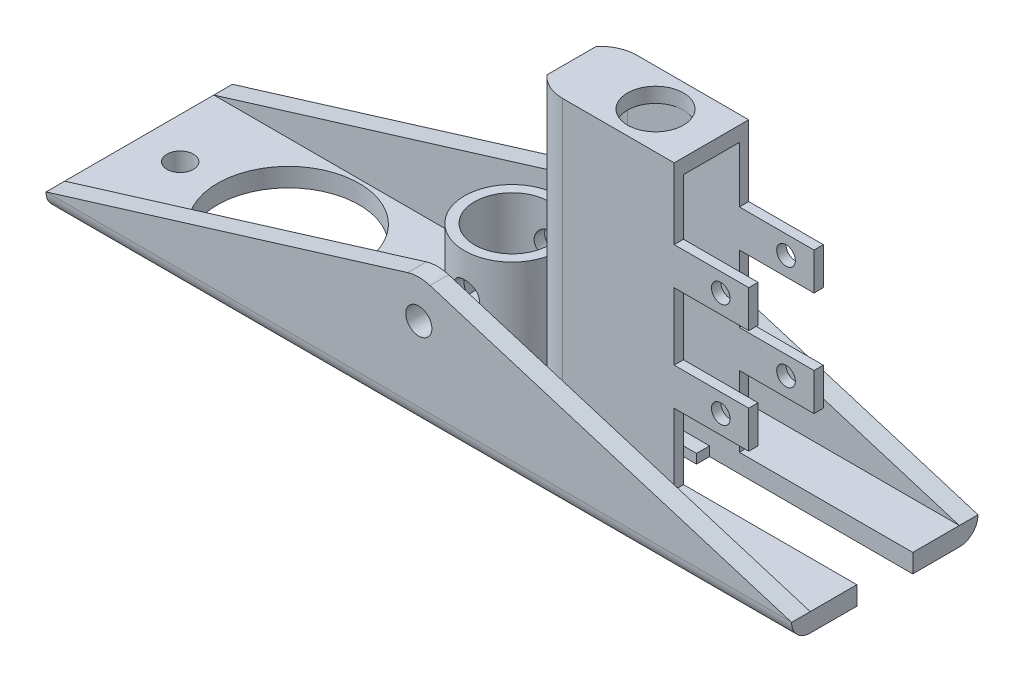
SolidWorks part; units mm, degrees
material "AISI 1035 Steel (SS)"
ref_plane "Front Plane" through (0, 0, 0) normal (0, 0, 1) x (1, 0, 0)
ref_plane "Top Plane" through (0, 0, 0) normal (0, 1, 0) x (1, 0, 0)
ref_plane "Right Plane" through (0, 0, 0) normal (1, 0, 0) x (0, 0, -1)
sketch "Sketch2" plane through (0, 0, 0) normal (0, 1, 0) x (1, 0, 0)
  line L0 (-100, -25) -> (100, -25)
  line L1 (100, -25) -> (100, 25)
  line L2 (100, 25) -> (-100, 25)
  line L3 (-100, 25) -> (-100, -25)
  line L4 (-60, 25) -> (-60, -25) construction
  line L6 (0, -55) -> (0, 55) construction
  circle A1 centre (-60, 0) radius 19
  circle A2 centre (-31, 0) radius 3.55
  circle A3 centre (-89, 0) radius 3.55
  point P6 (-100, 0)
  point P12 (0, 25)
  dimension "D4" = 38
  dimension "D5" = 7.1
  dimension "D1" = 200
  dimension "D2" = 50
  dimension "D6" = 29
  dimension "D3" = 60
extrude "Boss-Extrude1" add sketch "Sketch2" along normal blind 5
sketch "Sketch6" plane through (0, 0, 0) normal (0, 0, 1) x (1, 0, 0)
  line L0 (-100, 5) -> (-2.9907, 34.7517)
  line L1 (2.9907, 34.7517) -> (100, 5)
  line L2 (100, 5) -> (100, 0) construction
  line L3 (-100, 5) -> (100, 5)
  line L4 (-100, 5) -> (-100, 0) construction
  line L5 (55, 0) -> (-55, 0) construction
  arc A0 (2.9907, 34.7517) -> (-2.9907, 34.7517) centre (0, 25) ccw
  point P11 (0, 5)
  dimension "D1" = 20.4
  dimension "D2" = 20
  dimension "D4" = 5
extrude "Boss-Extrude3" add sketch "Sketch6" against normal up to surface and the other way up to surface up to face at (0, 2.5, -25) other way up to face at (0, 2.5, 25)
sketch "Sketch7" plane through (0, 0, 0) normal (0, 0, 1) x (1, 0, 0)
  line L0 (2.9907, 34.7517) -> (100, 5) construction
  line L1 (-100, 5) -> (-2.9907, 34.7517) construction
  line L2 (2.9907, 34.7517) -> (100, 5)
  line L3 (-100, 5) -> (-2.9907, 34.7517)
  line L4 (-100, 5) -> (100, 5)
  arc A0 (2.9907, 34.7517) -> (-2.9907, 34.7517) centre (0, 25) ccw construction
  arc A1 (2.9907, 34.7517) -> (-2.9907, 34.7517) centre (0, 25) ccw
extrude "Cut-Extrude2" cut sketch "Sketch7" against normal offset from surface 5 and the other way offset from surface 5 contours L2 A1 L3 L4 region at (0, 15.2168, 0) up to face at (0, 13.3253, -25) other way up to face at (0, 13.3253, 25)
sketch "Sketch22" [suppressed] plane through (0, 0, 0) normal (0, 0, 1) x (1, 0, 0)
  line L10 (-25.5, 27.8483) -> (-25.5, 5)
  line L11 (0, -19.36) -> (0, 19.36) construction
  line L13 (-100, 5) -> (-25.5, 5)
  line L14 (-100, 5) -> (-2.9907, 34.7517) construction
  line L15 (-25.5, 27.8483) -> (-100, 5)
  dimension "D1" = 25.5
extrude "Cut-Extrude9" [suppressed] cut sketch "Sketch22" against normal offset from surface 5 and the other way offset from surface 5
sketch "Sketch8" plane through (0, 5, 0) normal (0, 1, 0) x (1, 0, 0)
  circle A0 centre (0, 0) radius 10.05
  circle A1 centre (0, 0) radius 12.75
  dimension "D1" = 20.1
  dimension "D2" = 25.5
extrude "Boss-Extrude4" add sketch "Sketch8" along normal blind 30.2
fillet "Fillet1" radius 5 2 edges at (0, 0, -25) (0, 0, 25)
sketch "Sketch9" plane through (0, 0, 25) normal (0, 0, 1) x (1, 0, 0)
  line L0 (0, -55) -> (0, 55) construction
  line L1 (-100, 5) -> (100, 5) construction
  circle A0 centre (0, 25) radius 3.5
  dimension "D2" = 20
  dimension "D1" = 7
extrude "Cut-Extrude3" cut sketch "Sketch9" against normal through all
sketch "Sketch13" plane through (0, 5, 0) normal (0, 1, 0) x (1, 0, 0)
  line L0 (23.5, 0) -> (53.5, 0) construction
  line L1 (23.5, 7.5) -> (53.5, 7.5)
  line L2 (23.5, -7.5) -> (53.5, -7.5)
  arc A0 (23.5, 7.5) -> (23.5, -7.5) centre (23.5, 0) ccw
  arc A1 (53.5, -7.5) -> (53.5, 7.5) centre (53.5, 0) ccw
  circle A2 centre (31.5, 0) radius 2
  circle A4 centre (24.5, 0) radius 2
  circle A5 centre (38.5, 0) radius 2
  circle A6 centre (45.5, 0) radius 2
  circle A7 centre (52.5, 0) radius 2
  point P3 (38.5, 0)
  point P8 (16, 0)
  point P24 (38.5, 7.5)
  dimension "D3" = 16
  dimension "D4" = 4
  dimension "D1" = 30
  dimension "D2" = 7.5
  dimension "D6" = 7
  dimension "D5" = 5
extrude "Cut-Extrude5" cut sketch "Sketch13" against normal blind 2.5
sketch "Sketch15" plane through (0, 5, 0) normal (0, 1, 0) x (1, 0, 0)
  line L0 (23.5, 0) -> (53.5, 0) construction
  line L1 (23.5, 4) -> (53.5, 4)
  line L2 (23.5, -4) -> (53.5, -4)
  line L3 (53.5, 7.5) -> (23.5, 7.5) construction
  line L4 (53.5, 4) -> (100, 4)
  line L5 (100, 20) -> (100, -20) construction
  line L6 (100, 4) -> (100, -4)
  line L7 (100, -4) -> (53.5, -4)
  arc A5 (23.5, 4) -> (23.5, -4) centre (23.5, 0) ccw
  point P3 (38.5, 0)
  point P6 (100, 0)
  point P14 (38.5, 4)
  point P23 (38.5, 7.5)
  dimension "D1" = 30
  dimension "D3" = 4
  dimension "D2" = 8
extrude "Cut-Extrude6" cut sketch "Sketch15" against normal through all
sketch "Sketch16" plane through (0, 5, 0) normal (0, 1, 0) x (1, 0, 0)
  line L0 (16, -4) -> (16, -6.6144)
  line L9 (53.5, 7.5) -> (23.5, 7.5) construction
  line L10 (59.8443, 4) -> (23.5, 4) construction
  line L11 (23.5, -4) -> (59.8443, -4) construction
  line L15 (23.5, -7.5) -> (53.5, -7.5) construction
  line L16 (23.5, -7.5) -> (53.5, -7.5)
  line L17 (23.5, -10) -> (53.5, -10)
  line L18 (53.5, 10) -> (23.5, 10)
  line L19 (23.5, -10) -> (53.5, -10)
  line L20 (53.5, 10) -> (23.5, 10)
  line L21 (53.5, 7.5) -> (23.5, 7.5)
  line L22 (53.5, 10) -> (53.5, 7.5)
  line L23 (53.5, -7.5) -> (53.5, -10)
  line L24 (16, 6.6144) -> (16, 4)
  line L25 (17.1557, 4) -> (16, 4)
  line L26 (17.1557, -4) -> (16, -4)
  arc A0 (17.1557, -4) -> (23.5, -7.5) centre (23.5, 0) ccw
  arc A1 (23.5, 7.5) -> (23.5, -7.5) centre (23.5, 0) ccw construction
  arc A2 (23.5, 10) -> (23.5, -10) centre (23.5, 0) ccw
  arc A3 (23.5, 10) -> (16, 6.6144) centre (23.5, 0) ccw
  arc A4 (23.5, 7.5) -> (17.1557, 4) centre (23.5, 0) ccw
  arc A5 (16, -6.6144) -> (23.5, -10) centre (23.5, 0) ccw
  point P10 (16, 0)
  dimension "D1" = 2.5
extrude "Boss-Extrude7" add sketch "Sketch16" along normal blind 72
sketch "Sketch17" plane through (0, 77, 0) normal (0, 1, 0) x (1, 0, 0)
  line L0 (23.5, -10) -> (53.5, -10) construction
  line L1 (53.5, 10) -> (23.5, 10) construction
  line L2 (23.5, -10) -> (53.5, -10)
  line L3 (53.5, 10) -> (23.5, 10)
  line L4 (16, -4) -> (16, -6.6144) construction
  line L6 (16, 6.6144) -> (16, 4) construction
  line L8 (16, -4) -> (16, -6.6144)
  line L10 (16, 6.6144) -> (16, 4)
  line L12 (16, 4) -> (16, -4)
  line L13 (53.5, 10) -> (53.5, -10)
  arc A2 (53.5, 10) -> (53.5, -10) centre (53.5, 0) cw construction
  circle A3 centre (38.5, 0) radius 7.5
  arc A4 (16, -6.6144) -> (23.5, -10) centre (23.5, 0) ccw construction
  arc A5 (23.5, 10) -> (16, 6.6144) centre (23.5, 0) ccw construction
  arc A6 (16, -6.6144) -> (23.5, -10) centre (23.5, 0) ccw
  arc A7 (23.5, 10) -> (16, 6.6144) centre (23.5, 0) ccw
  point P9 (38.5, 10)
  dimension "D1" = 15
extrude "Boss-Extrude8" add sketch "Sketch17" along normal blind 4
sketch "Sketch18" plane through (0, 5, 0) normal (0, 1, 0) x (1, 0, 0)
  circle A0 centre (0, 0) radius 10.05
  circle A1 centre (0, 0) radius 10.05 construction
extrude "Boss-Extrude9" add sketch "Sketch18" along normal blind 9.5
sketch "Sketch19" plane through (53.5, 0, 0) normal (1, 0, 0) x (0, 0, -1)
  line L0 (-10, 81) -> (-10, 5) construction
  line L1 (-10, 62) -> (-7.5, 62)
  line L2 (-10, 62) -> (-10, 52)
  line L3 (-10, 52) -> (-7.5, 52)
  line L4 (-7.5, 62) -> (-7.5, 52)
  line L5 (-7.5, 77) -> (-7.5, 5) construction
  line L6 (7.5, 77) -> (7.5, 5) construction
  line L7 (7.5, 62) -> (10, 62)
  line L8 (7.5, 62) -> (7.5, 52)
  line L9 (7.5, 52) -> (10, 52)
  line L10 (10, 62) -> (10, 52)
  line L11 (10, 81) -> (10, 5) construction
  line L12 (7.5, 77) -> (-7.5, 77) construction
  line L13 (-10, 43) -> (10, 43) construction
  line L14 (-10, 81) -> (-10, 5) construction
  line L15 (10, 81) -> (10, 5) construction
  line L16 (7.5, 34) -> (10, 34)
  line L17 (10, 24) -> (10, 34)
  line L18 (7.5, 24) -> (10, 24)
  line L19 (7.5, 24) -> (7.5, 34)
  line L20 (-10, 34) -> (-7.5, 34)
  line L21 (-7.5, 24) -> (-7.5, 34)
  line L22 (-10, 24) -> (-7.5, 24)
  line L23 (-10, 24) -> (-10, 34)
  dimension "D1" = 10
  dimension "D2" = 15
extrude "Boss-Extrude10" add sketch "Sketch19" along normal blind 20
sketch "Sketch20" plane through (0, 0, 10) normal (0, 0, 1) x (1, 0, 0)
  line L0 (53.5, 43) -> (73.5, 43) construction
  line L1 (53.5, 52) -> (53.5, 34) construction
  line L2 (73.5, 62) -> (73.5, 52) construction
  line L3 (53.5, 52) -> (53.5, 34) construction
  circle A0 centre (66, 57) radius 2.5
  circle A1 centre (66, 29) radius 2.5
  point P6 (73.5, 57)
  dimension "D1" = 5
  dimension "D2" = 12.5
extrude "Cut-Extrude7" cut sketch "Sketch20" against normal through all
sketch "Sketch21" plane through (100, 0, 0) normal (1, 0, 0) x (0, 0, -1)
  line L0 (-20, 0) -> (-4, 0) construction
  line L1 (-4, 5) -> (-7.5, 5)
  line L2 (-4, 5) -> (-4, 0)
  line L3 (-4, 0) -> (-7.5, 0)
  line L4 (-7.5, 5) -> (-7.5, 0)
  line L6 (4, 5) -> (7.5, 5)
  line L7 (4, 5) -> (4, 0)
  line L8 (4, 0) -> (7.5, 0)
  line L9 (7.5, 5) -> (7.5, 0)
  line L10 (7.5, 2.5) -> (7.5, 77) construction
  line L11 (-7.5, 2.5) -> (-7.5, 77) construction
  line L12 (4, 0) -> (20, 0) construction
extrude "Cut-Extrude8" cut sketch "Sketch21" against normal offset from surface (54.5 mm away) 8 up to face at (53.5, 14.5, 8.75) offset beyond the face yes
equation "\"H\"=20"
equation "\"D2@Sketch6\"=\"H\""
equation "\"Height\"= \"H\" + 10.2"
equation "\"D2@Sketch9\"=\"H\""
equation "\"D1@Boss-Extrude4\"=\"Height\""
equation "\"Length\"=200"
equation "\"D1@Sketch2\"=\"Length\""
equation "\"Width\"=50"
equation "\"D2@Sketch2\"=\"Width\""
equation "\"CylWidth\"=20.1"
equation "\"D1@Sketch8\"=\"CylWidth\""
equation "\"D2@Sketch8\"   = \"CylWidth\"+10"
equation "\"HoleWidth\"=38"
equation "\"D4@Sketch2\"=\"HoleWidth\""
equation "\"HoleDist\"= 35"
